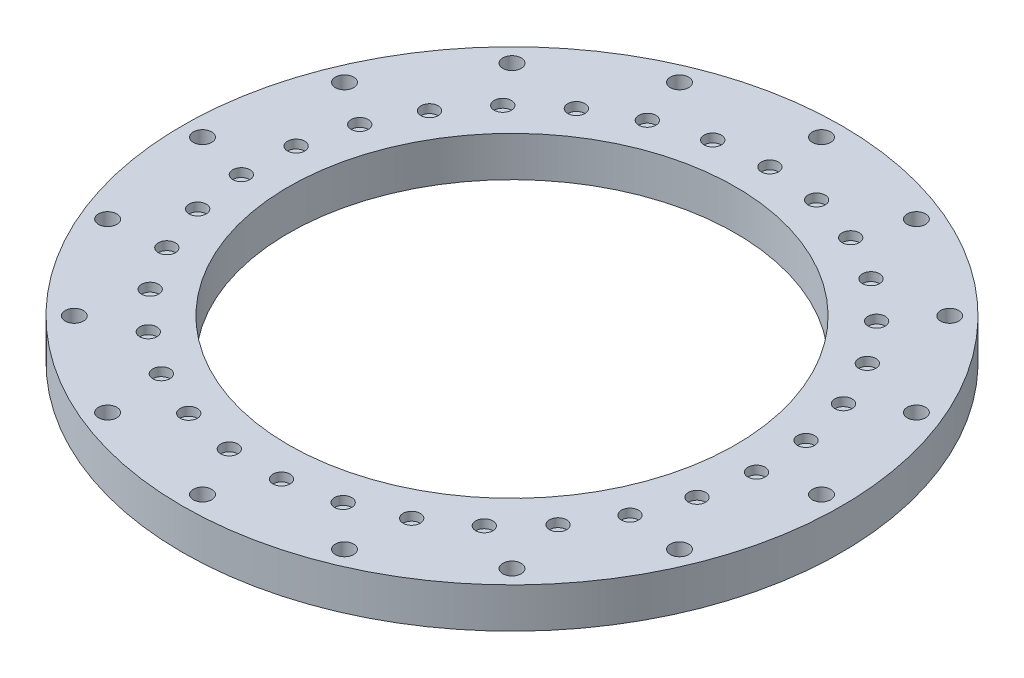
SolidWorks part; units mm, degrees
ref_plane "Front Plane" through (0, 0, 0) normal (0, 0, 1) x (1, 0, 0)
ref_plane "Top Plane" through (0, 0, 0) normal (0, 1, 0) x (1, 0, 0)
ref_plane "Right Plane" through (0, 0, 0) normal (1, 0, 0) x (0, 0, -1)
sketch "Sketch1" plane through (0, 0, 0) normal (0, 1, 0) x (1, 0, 0)
  circle A0 centre (0, 0) radius 57.5
  circle A1 centre (0, 0) radius 39
  dimension "D1" = 115
  dimension "D2" = 78
extrude "Boss-Extrude1" add sketch "Sketch1" along normal blind 7
sketch "Sketch2" plane through (0, 7, 0) normal (0, 1, 0) x (1, 0, 0)
  circle A0 centre (0, 0) radius 54 construction
  circle A1 centre (0, 54) radius 1.6
  circle A2 centre (20.6649, 49.8895) radius 1.6
  circle A3 centre (38.1838, 38.1838) radius 1.6
  circle A4 centre (49.8895, 20.6649) radius 1.6
  circle A5 centre (54, 0) radius 1.6
  circle A6 centre (49.8895, -20.6649) radius 1.6
  circle A7 centre (38.1838, -38.1838) radius 1.6
  circle A8 centre (20.6649, -49.8895) radius 1.6
  circle A9 centre (0, -54) radius 1.6
  circle A10 centre (-20.6649, -49.8895) radius 1.6
  circle A11 centre (-38.1838, -38.1838) radius 1.6
  circle A12 centre (-49.8895, -20.6649) radius 1.6
  circle A13 centre (-54, 0) radius 1.6
  circle A14 centre (-49.8895, 20.6649) radius 1.6
  circle A15 centre (-38.1838, 38.1838) radius 1.6
  circle A16 centre (-20.6649, 49.8895) radius 1.6
  point P37 (0, 0)
  dimension "D1" = 108
  dimension "D2" = 3.2
  dimension "D3" = 16
extrude "Cut-Extrude1" cut sketch "Sketch2" against normal blind 17
sketch "Sketch3" plane through (0, 7, 0) normal (0, 1, 0) x (1, 0, 0)
  circle A0 centre (0, 0) radius 45 construction
  circle A1 centre (0, 45) radius 1.5
  circle A2 centre (9.0584, 44.0788) radius 1.5
  circle A3 centre (17.746, 41.3531) radius 1.5
  circle A4 centre (25.7071, 36.9344) radius 1.5
  circle A5 centre (32.6157, 31.0035) radius 1.5
  circle A6 centre (38.189, 23.8034) radius 1.5
  circle A7 centre (42.1988, 15.6287) radius 1.5
  circle A8 centre (44.4811, 6.8142) radius 1.5
  circle A9 centre (44.9422, -2.2792) radius 1.5
  circle A10 centre (43.5635, -11.2794) radius 1.5
  circle A11 centre (40.4012, -19.8177) radius 1.5
  circle A12 centre (35.5849, -27.5448) radius 1.5
  circle A13 centre (29.3118, -34.1441) radius 1.5
  circle A14 centre (21.8386, -39.3456) radius 1.5
  circle A15 centre (13.4713, -42.9363) radius 1.5
  circle A16 centre (4.5526, -44.7691) radius 1.5
  circle A17 centre (-4.5526, -44.7691) radius 1.5
  circle A18 centre (-13.4713, -42.9363) radius 1.5
  circle A19 centre (-21.8386, -39.3456) radius 1.5
  circle A20 centre (-29.3118, -34.1441) radius 1.5
  circle A21 centre (-35.5849, -27.5448) radius 1.5
  circle A22 centre (-40.4012, -19.8177) radius 1.5
  circle A23 centre (-43.5635, -11.2794) radius 1.5
  circle A24 centre (-44.9422, -2.2792) radius 1.5
  circle A25 centre (-44.4811, 6.8142) radius 1.5
  circle A26 centre (-42.1988, 15.6287) radius 1.5
  circle A27 centre (-38.189, 23.8034) radius 1.5
  circle A28 centre (-32.6157, 31.0035) radius 1.5
  circle A29 centre (-25.7071, 36.9344) radius 1.5
  circle A30 centre (-17.746, 41.3531) radius 1.5
  circle A31 centre (-9.0584, 44.0788) radius 1.5
  point P67 (0, 0)
  dimension "D1" = 90
  dimension "D2" = 3
  dimension "D3" = 31
extrude "Cut-Extrude2" cut sketch "Sketch3" against normal blind 1.5
